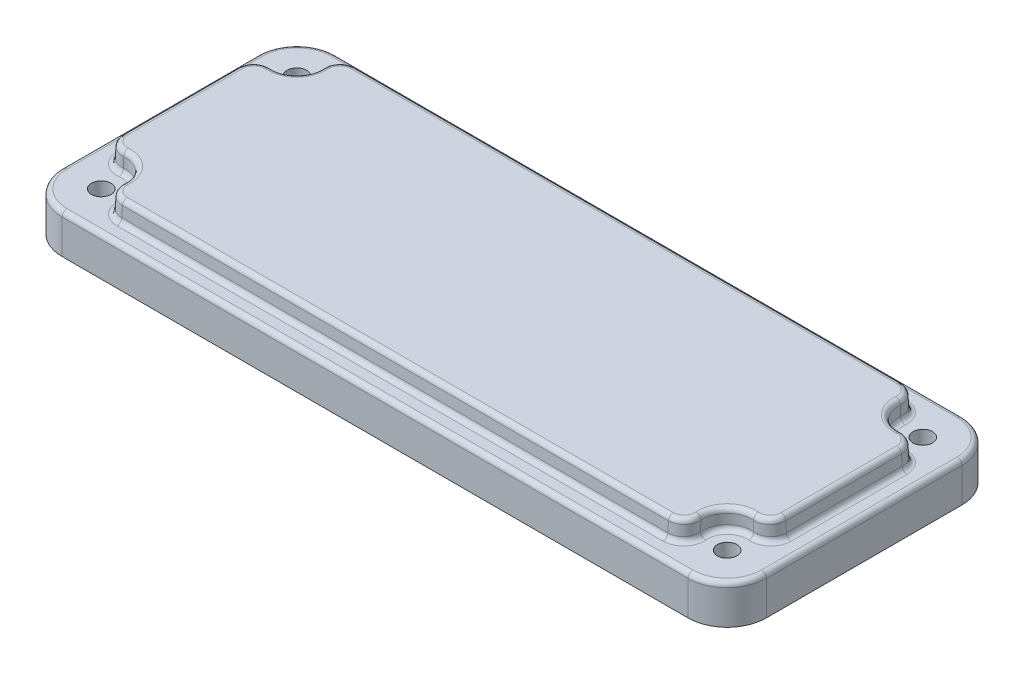
SolidWorks part; units mm, degrees
material "PW20:29:Sc:0:"
ref_plane "Front" through (0, 0, 0) normal (0, 0, 1) x (1, 0, 0)
ref_plane "Top" through (0, 0, 0) normal (0, 1, 0) x (1, 0, 0)
ref_plane "Right" through (0, 0, 0) normal (1, 0, 0) x (0, 0, -1)
other "Configuration Table"
sketch "Sketch1" plane through (0, 0, 0) normal (0, 1, 0) x (1, 0, 0)
  line L0 (-50.8, 22.225) -> (50.8, 22.225)
  line L1 (-57.15, 15.875) -> (-57.15, -15.875)
  line L2 (50.8, -22.225) -> (-50.8, -22.225)
  line L3 (57.15, -15.875) -> (57.15, 15.875)
  line L4 (-50.8, -15.875) -> (50.8, 15.875) construction
  arc A0 (-57.15, -15.875) -> (-50.8, -22.225) centre (-50.8, -15.875) ccw
  arc A1 (57.15, -15.875) -> (50.8, -22.225) centre (50.8, -15.875) cw
  arc A2 (50.8, 22.225) -> (57.15, 15.875) centre (50.8, 15.875) cw
  arc A3 (-50.8, 22.225) -> (-57.15, 15.875) centre (-50.8, 15.875) ccw
  dimension "D1" = 114.3
  dimension "D2" = 44.45
  dimension "D4" = 6.35
extrude "Base-Extrude" add sketch "Sketch1" along normal blind 6.35
sketch "Sketch2" plane through (0, 6.35, 0) normal (0, 1, 0) x (-1, 0, 0)
  line L4 (50.8, 19.05) -> (-50.8, 19.05)
  line L5 (-53.975, 15.875) -> (-53.975, -15.875)
  line L6 (-50.8, -19.05) -> (50.8, -19.05)
  line L7 (53.975, -15.875) -> (53.975, 15.875)
  line L8 (50.8, 19.05) -> (-50.8, 19.05)
  line L9 (-53.975, 15.875) -> (-53.975, -15.875)
  line L10 (-50.8, -19.05) -> (50.8, -19.05)
  line L11 (53.975, -15.875) -> (53.975, 15.875)
  arc A4 (53.975, 15.875) -> (50.8, 19.05) centre (50.8, 15.875) ccw
  arc A5 (53.975, 15.875) -> (50.8, 19.05) centre (50.8, 15.875) ccw
  arc A6 (-50.8, 19.05) -> (-53.975, 15.875) centre (-50.8, 15.875) ccw
  arc A7 (-50.8, 19.05) -> (-53.975, 15.875) centre (-50.8, 15.875) ccw
  arc A8 (-53.975, -15.875) -> (-50.8, -19.05) centre (-50.8, -15.875) ccw
  arc A9 (-53.975, -15.875) -> (-50.8, -19.05) centre (-50.8, -15.875) ccw
  arc A10 (50.8, -19.05) -> (53.975, -15.875) centre (50.8, -15.875) ccw
  arc A11 (50.8, -19.05) -> (53.975, -15.875) centre (50.8, -15.875) ccw
  dimension "D1" = 3.175
extrude "Boss-Extrude1" add sketch "Sketch2" along normal blind 3.175 draft 3
sketch "Sketch3" plane through (0, 9.525, 0) normal (0, 1, 0) x (-1, 0, 0)
  circle A0 centre (-50.8, 15.875) radius 3.9687
  dimension "D1" = 7.9375
extrude "Cut-Extrude1" cut sketch "Sketch3" against normal up to surface (3.175 mm away)
sketch "Sketch4" plane through (0, 6.35, 0) normal (0, 1, 0) x (-1, 0, 0)
  circle A0 centre (-50.8, 15.875) radius 1.5875
  dimension "D1" = 3.175
extrude "Cut-Extrude2" cut sketch "Sketch4" against normal through all
mirror "Mirror1" about plane through (0, 0, 0) normal (0, 0, 1) of "Cut-Extrude2", "Cut-Extrude1"
mirror "Mirror2" about plane through (0, 0, 0) normal (1, 0, 0) of "Mirror1"
fillet "Fillet1" radius 2.54 8 edges at (48.3138, 7.9044, 18.9685) (53.8935, 7.9044, 13.3888) (53.8935, 7.9044, -13.3888) (48.3138, 7.9044, -18.9685) (-48.3138, 7.9044, -18.9685) (-53.8935, 7.9044, -13.3888) (-53.8935, 7.9044, 13.3888) (-48.3138, 7.9044, 18.9685)
fillet "Fillet2" radius 0.7937 40 edges at (0, 6.35, -19.05) (0, 9.525, -18.8836) (-46.2625, 6.35, -18.1482) (46.1444, 6.35, -18.2787) (-45.8933, 9.525, -18.3276) (46.3986, 9.525, -17.785) (-47.9937, 6.35, -13.0687) (47.9937, 6.35, -13.0687) (-47.9937, 9.525, -13.0687) (47.9937, 9.525, -13.0687) (-53.2213, 6.35, -11.2022) (53.0648, 6.35, -11.3446) (-52.71, 9.525, -11.4736) (53.2526, 9.525, -10.9683) (0, 6.35, -22.225) (-53.975, 6.35, 0) (53.975, 6.35, 0) (-53.8086, 9.525, 0) (53.8086, 9.525, 0) (55.2901, 6.35, -20.3651) (-55.2901, 6.35, -20.3651) (-53.0383, 6.35, 11.3664) (53.2408, 6.35, 11.1827) (-53.2526, 9.525, 10.9683) (52.71, 9.525, 11.4736) (57.15, 6.35, 0) (-57.15, 6.35, 0) (-47.9937, 6.35, 13.0687) (47.9937, 6.35, 13.0687) (-47.9937, 9.525, 13.0687) (47.9937, 9.525, 13.0687) (55.2901, 6.35, 20.3651) (-55.2901, 6.35, 20.3651) (-46.1066, 6.35, 18.3169) (46.2919, 6.35, 18.1127) (-46.3986, 9.525, 17.785) (45.8933, 9.525, 18.3276) (0, 6.35, 22.225) (0, 6.35, 19.05) (0, 9.525, 18.8836)
sketch "Sketch5" plane through (0, 0, 0) normal (0, -1, 0) x (1, 0, 0)
  line L0 (-44.45, 15.875) -> (44.45, 15.875)
  line L1 (-44.45, 15.875) -> (-44.45, -15.875)
  line L2 (44.45, -15.875) -> (-44.45, -15.875)
  line L3 (44.45, -15.875) -> (44.45, 15.875)
  line L4 (50.8, 22.225) -> (-50.8, 22.225) construction
  line L5 (57.15, 15.875) -> (57.15, -15.875) construction
  line L6 (-57.15, -15.875) -> (-57.15, 15.875) construction
  line L7 (-50.8, -22.225) -> (50.8, -22.225) construction
  dimension "D1" = 6.35
  dimension "D2" = 12.7
  dimension "D3" = 12.7
  dimension "D4" = 6.35
extrude "Cut-Extrude3" cut sketch "Sketch5" against normal blind 6.35 draft 3
fillet "Fillet3" radius 6.35 4 edges at (44.2836, 3.175, 15.7086) (44.2836, 3.175, -15.7086) (-44.2836, 3.175, 15.7086) (-44.2836, 3.175, -15.7086)
fillet "Fillet4" radius 3.175 8 edges at (44.1172, 6.35, 0) (42.2609, 6.35, 13.6859) (42.2609, 6.35, -13.6859) (0, 6.35, 15.5422) (0, 6.35, -15.5422) (-42.2609, 6.35, 13.6859) (-42.2609, 6.35, -13.6859) (-44.1172, 6.35, 0)
